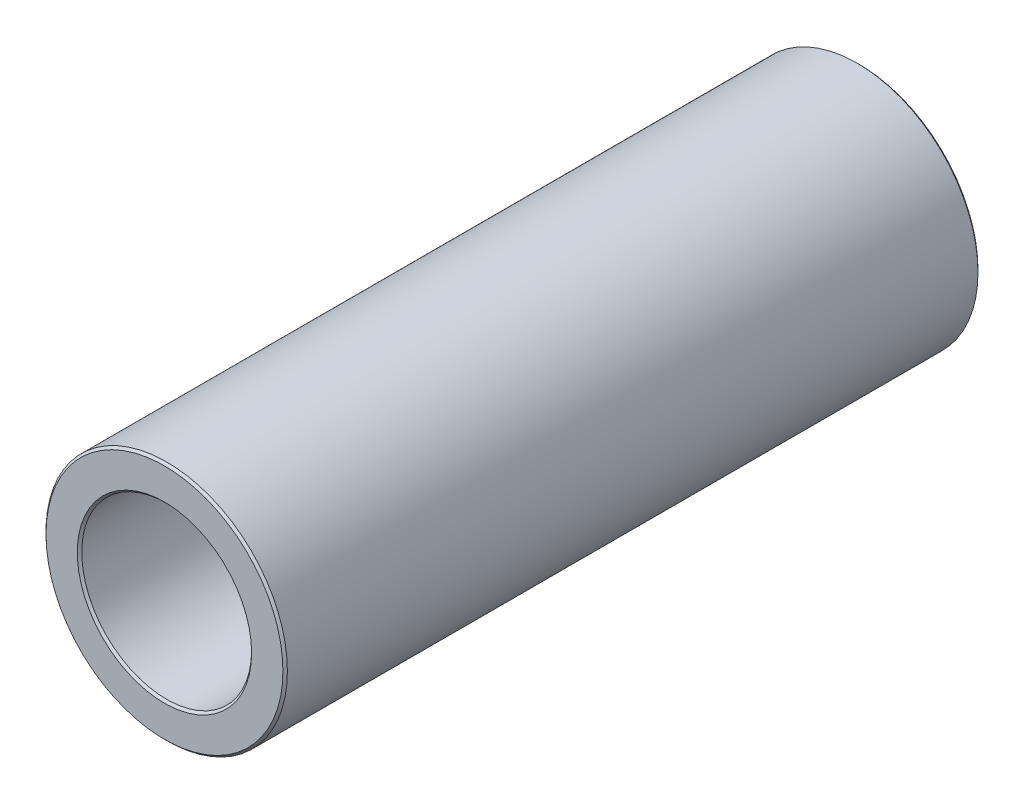
SolidWorks part; units mm, degrees
material "1.0037 (S235JR)"
ref_plane "E_Rechts" through (0, 0, 0) normal (0, 0, 1) x (1, 0, 0)
ref_plane "E_Oben" through (0, 0, 0) normal (0, 1, 0) x (1, 0, 0)
ref_plane "E_Vorne" through (0, 0, 0) normal (1, 0, 0) x (0, 0, -1)
ref_axis "A_Drehachse" through (0, 0, 55) along (0, 0, -1)
sketch "Skizze1" plane through (0, 0, 0) normal (0, 0, 1) x (1, 0, 0)
  circle A0 centre (0, 0) radius 27
  circle A1 centre (0, 0) radius 19
  dimension "D1" = 54
  dimension "D2" = 38
extrude "Aufsatz-Linear austragen1" add sketch "Skizze1" along normal blind 79 and the other way blind 76.5
chamfer "Fase1" distance 0.5 angle 45 4 edges at (27, 0, -76.5) (27, 0, 79) (19, 0, -76.5) (19, 0, 79)
